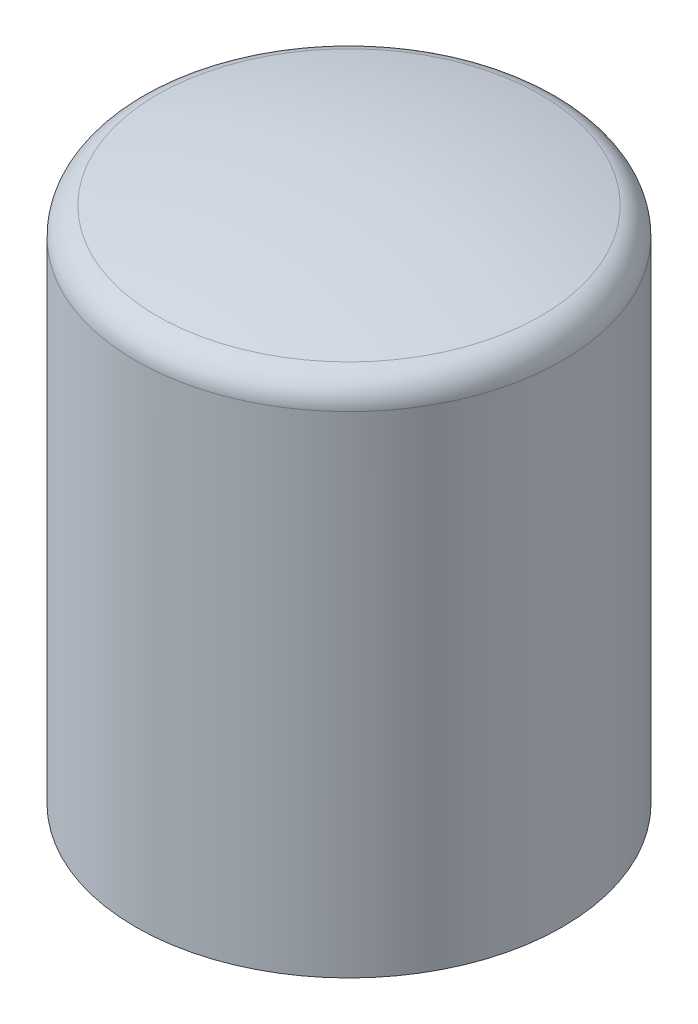
SolidWorks part; units mm, degrees
ref_plane "Front Plane" through (0, 0, 0) normal (0, 0, 1) x (1, 0, 0)
ref_plane "Top Plane" through (0, 0, 0) normal (0, 1, 0) x (1, 0, 0)
ref_plane "Right Plane" through (0, 0, 0) normal (1, 0, 0) x (0, 0, -1)
sketch "Sketch1" plane through (0, 0, 0) normal (0, 1, 0) x (1, 0, 0)
  circle A0 centre (0, 0) radius 7.5
  dimension "D1" = 15
extrude "Boss-Extrude1" add sketch "Sketch1" along normal blind 18
dome "Dome1" faces to dome 1 distance 1 reverse direction no elliptical dome no face at (0, 18, 7.5) parameters "D1"=1
fillet "Fillet1" radius 1 1 edges at (0, 18, 7.5)
sketch "Sketch2" plane through (0, 0, 0) normal (0, -1, 0) x (1, 0, 0)
  circle A0 centre (0, 0) radius 3.3
  dimension "D1" = 6.6
extrude "Cut-Extrude1" cut sketch "Sketch2" against normal blind 6.35
sketch "Sketch3" plane through (0, 6.35, 0) normal (0, -1, 0) x (1, 0, 0)
  line L0 (0, 0) -> (-3.3, 0) construction
  line L1 (2.56, 2.0824) -> (4.04, 2.0824)
  line L2 (2.56, 2.0824) -> (2.56, -2.0824)
  line L3 (2.56, -2.0824) -> (4.04, -2.0824)
  line L4 (4.04, 2.0824) -> (4.04, -2.0824)
  line L5 (2.56, 2.0824) -> (4.04, -2.0824) construction
  line L6 (2.56, -2.0824) -> (4.04, 2.0824) construction
  circle A0 centre (0, 0) radius 3.3 construction
  circle A1 centre (0, 0) radius 3.3 construction
  point P0 (3.3, 0)
  dimension "D1" = 5.86
extrude "Boss-Extrude2" add sketch "Sketch3" along normal up to surface (6.35 mm away) up to face at (0, 0, -3.3)
